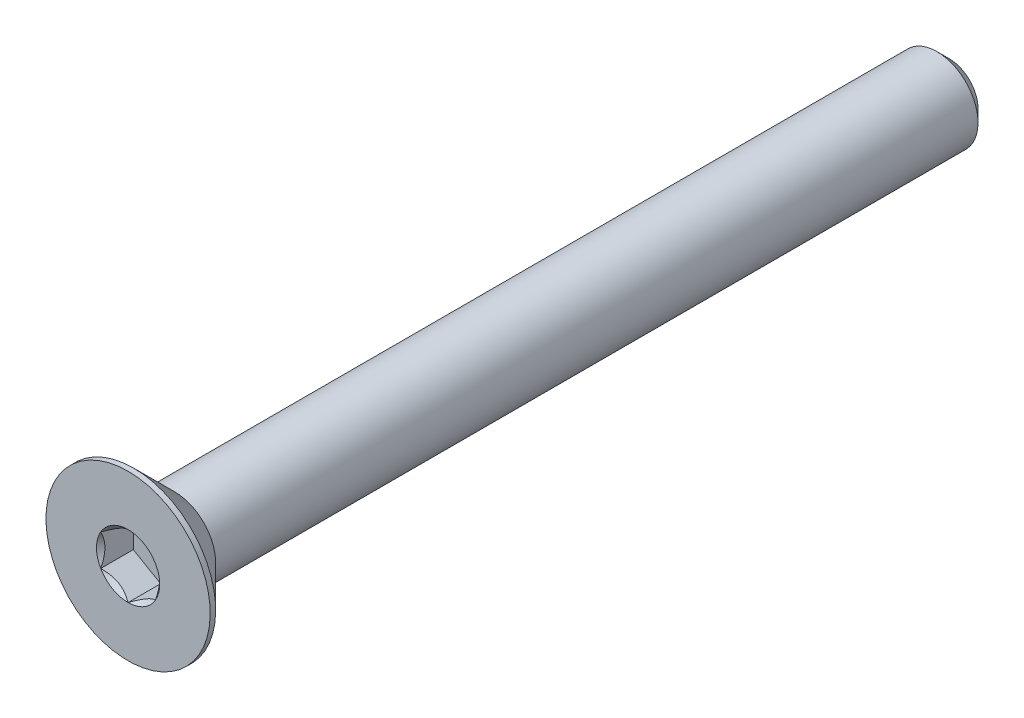
SolidWorks part; units mm, degrees
material "Alloy Steel"
ref_plane "Front" through (0, 0, 0) normal (0, 0, 1) x (1, 0, 0)
ref_plane "Top" through (0, 0, 0) normal (0, 1, 0) x (1, 0, 0)
ref_plane "Right" through (0, 0, 0) normal (1, 0, 0) x (0, 0, -1)
sketch "Sketch1" plane through (0, 0, 0) normal (1, 0, 0) x (0, 0, -1)
  line L0 (-15, 3) -> (-14.8, 3) construction
  line L1 (-14.8, 3) -> (-13.3, 1.5) construction
  line L2 (-15, 1.5) -> (15, 1.5) construction
  line L3 (15, 1.5) -> (15, 0) construction
  line L4 (15, 0) -> (-15, 0) construction
  line L5 (-15, 0) -> (-15, 3) construction
  line L6 (-15, 3) -> (-15, -3) construction
  line L7 (15, 1.5) -> (15, -1.5) construction
  line L8 (-15, -3) -> (-14.8, -3) construction
  line L9 (-14.8, -3) -> (-13.3, -1.5) construction
  line L11 (-15, 1.5) -> (-15, 0) construction
  line L12 (-13.3, 1.5) -> (-13.3, 0) construction
  line L13 (14.9688, 1.5541) -> (15.2188, 1.1211) construction
  line L14 (15.2188, 1.1211) -> (15.4688, 1.5541) construction
  line L15 (15.4688, 1.5541) -> (14.9688, 1.5541) construction
  line L16 (15.2188, 1.5541) -> (15.2188, 1.5) construction
  line L17 (15.2188, 1.5) -> (15.2188, 1.1752) construction
  line L18 (15.2188, 1.1752) -> (15.2188, 1.1211) construction
  line L19 (15.2188, 1.5271) -> (15.4531, 1.5271) construction
  line L20 (15.2188, 1.5271) -> (14.9844, 1.5271) construction
  line L21 (15, 1.5) -> (15.4375, 1.5) construction
  line L22 (15.1875, 1.1752) -> (15.25, 1.1752) construction
  line L23 (15, -1.5) -> (-13.3, -1.5) construction
  point P10 (13.75, -1.5)
  point P24 (-13.3, 1.5)
  point P30 (0, 0)
  dimension "Head Diameter" = 6
  dimension "Head Height" = 1.7
  dimension "Length" = 30
  dimension "Countersink Angle" = 90
  dimension "Thread Pitch" = 0.5
  dimension "D2" = 0.0625
  dimension "Minimum Thread Length" = 28.3
  dimension "Thread Size" = 3
  dimension "D1" = 1.25
sketch "Sketch2" plane through (0, 0, 0) normal (0, 0, 1) x (1, 0, 0)
  line L1 (0, 1.1547) -> (-1, 0.5774) construction
  line L2 (-1, 0.5774) -> (-1, -0.5774) construction
  line L3 (-1, -0.5774) -> (0, -1.1547) construction
  line L4 (0, -1.1547) -> (1, -0.5774) construction
  line L5 (1, -0.5774) -> (1, 0.5774) construction
  line L6 (1, 0.5774) -> (0, 1.1547) construction
  circle A0 centre (0, 0) radius 1 construction
  dimension "Drive Size" = 2
sketch "Sketch3" plane through (0, 0, 0) normal (1, 0, 0) x (0, 0, -1)
  line L0 (-15, 1.5) -> (15, 1.5)
  line L1 (15, 1.5) -> (15, 0)
  line L2 (15, 0) -> (-15, 0)
  line L3 (-15, 0) -> (-15, 1.5)
revolve "Revolve1" add sketch "Sketch3" angle 360 about L4
chamfer "Chamfer1" distance 0.45 angle 45 1 edges at (0, 1.5, -15)
sketch "Sketch6" plane through (0, 0, 0) normal (1, 0, 0) x (0, 0, -1)
  line L0 (-15, 3) -> (-14.8, 3)
  line L1 (-14.8, 3) -> (-13.3, 1.5)
  line L2 (-13.3, 1.5) -> (-13.3, 0)
  line L3 (-13.3, 0) -> (-15, 0)
  line L4 (-15, 0) -> (-15, 3)
revolve "Revolve2" add sketch "Sketch6" angle 360 about L4
sketch "Sketch8" plane through (0, 0, 15) normal (0, 0, 1) x (1, 0, 0)
  line L0 (0, 1.1547) -> (-1, 0.5774) construction
  line L1 (1, 0.5774) -> (0, 1.1547) construction
  line L2 (1, -0.5774) -> (1, 0.5774) construction
  line L3 (0, -1.1547) -> (1, -0.5774) construction
  line L4 (-1, 0.5774) -> (-1, -0.5774) construction
  line L5 (-1, -0.5774) -> (0, -1.1547) construction
  line L6 (0, 1.1547) -> (-1, 0.5774)
  line L7 (1, 0.5774) -> (0, 1.1547)
  line L8 (1, -0.5774) -> (1, 0.5774)
  line L9 (0, -1.1547) -> (1, -0.5774)
  line L10 (-1, 0.5774) -> (-1, -0.5774)
  line L11 (-1, -0.5774) -> (0, -1.1547)
extrude "Cut-Extrude1" cut sketch "Sketch8" against normal blind 1.19
sketch "Sketch9" plane through (0, 0, 15) normal (0, 0, 1) x (1, 0, 0)
  circle A0 centre (0, 0) radius 1.1547
extrude "Cut-Extrude2" cut sketch "Sketch9" against normal up to next (1.19 mm away) draft 45
ref_plane "Plane1" [suppressed] through (0, 0, 13.3) normal (0, 0, 1) x (1, 0, 0)
split "Split1" [suppressed] bodies to split 124
sketch "Sketch4" [suppressed] plane through (0, 0, -15) normal (0, 0, -1) x (-1, 0, 0)
  circle A0 centre (0, 0) radius 1.5 construction
  circle A1 centre (0, 0) radius 1.5
curve "Helix/Spiral1" [suppressed] pitch 0.5 height 28.8 turns 57.6
sketch "Sketch10" [suppressed] plane through (0, 0, 0) normal (1, 0, 0) x (0, 0, -1)
  line L0 (14.9844, 1.5271) -> (15.4531, 1.5271)
  line L1 (15.4531, 1.5271) -> (15.25, 1.1752)
  line L2 (15.25, 1.1752) -> (15.1875, 1.1752)
  line L3 (15.1875, 1.1752) -> (14.9844, 1.5271)
sweep "Cut-Sweep1" [suppressed] cut profiles "Sketch10" path "Helix/Spiral1"
equation "\"D2@Sketch1\" = \"Thread Pitch@Sketch1\" / 8"
equation "\"D4@Helix/Spiral1\"=\"Thread Pitch@Sketch1\""
equation "\"D3@Helix/Spiral1\"=\"Minimum Thread Length@Sketch1\"+\"Thread Pitch@Sketch1\""
equation "\"D1@Chamfer1\"=\"Thread Size@Sketch1\"*.15"
equation "\"D1@Cut-Extrude1\"=\"Head Height@Sketch1\"*.7"
equation "\"D1@Sketch1\"=\"Thread Pitch@Sketch1\"*2.5"
